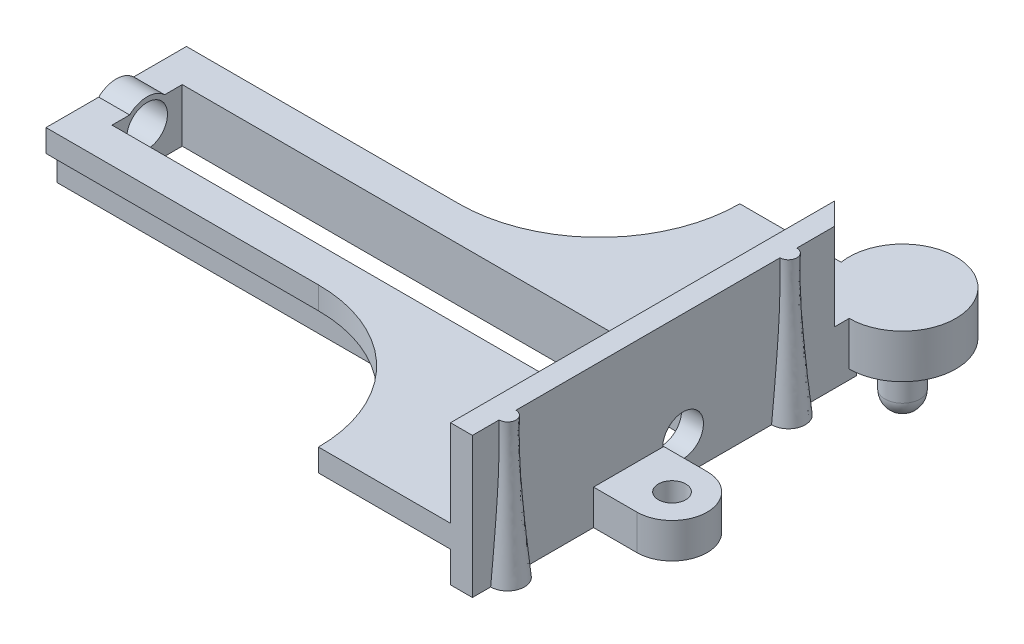
SolidWorks part; units mm, degrees
ref_plane "Alzado" through (0, 0, 0) normal (0, 0, 1) x (1, 0, 0)
ref_plane "Planta" through (0, 0, 0) normal (0, 1, 0) x (1, 0, 0)
ref_plane "Vista lateral" through (0, 0, 0) normal (1, 0, 0) x (0, 0, -1)
sketch "Sketch1" plane through (0, 0, 0) normal (1, 0, 0) x (0, 0, -1)
  line L1 (-10.668, -4.826) -> (10.668, -4.826)
  line L2 (-12.7, 0.762) -> (-12.7, 4.826)
  line L3 (-12.7, 4.826) -> (-3.1623, 4.826)
  line L6 (0, -4.826) -> (0, 12.0832) construction
  line L7 (-10.668, -4.826) -> (-10.668, 0.762)
  line L9 (-10.668, 0.762) -> (-12.7, 0.762)
  line L13 (10.668, 0.762) -> (12.7, 0.762)
  line L14 (10.668, -4.826) -> (10.668, 0.762)
  line L15 (12.7, 4.826) -> (3.1623, 4.826)
  line L16 (12.7, 0.762) -> (12.7, 4.826)
  arc A0 (3.1623, 4.826) -> (-3.1623, 4.826) centre (0, 1.524) ccw
  point P0 (0, 0)
  dimension "D5" = 9.144
extrude "Boss-Extrude1" add sketch "Sketch1" along normal blind 98.552
sketch "Sketch2" plane through (0, 4.826, 0) normal (0, 1, 0) x (1, 0, 0)
  line L0 (0, 0) -> (5.588, 0)
  line L1 (5.588, -6.35) -> (5.588, 6.35)
  line L2 (5.588, 6.35) -> (98.552, 6.35)
  line L3 (98.552, 12.7) -> (98.552, 3.1623) construction
  line L4 (5.588, -6.35) -> (98.552, -6.35)
  line L5 (98.552, -3.1623) -> (98.552, -12.7) construction
  line L6 (98.552, -6.35) -> (98.552, 6.35)
  point P6 (5.588, 0)
  line M6 (98.552, -12.7) -> (98.552, -3.1623)
  line M7 (98.552, -3.1623) -> (0, -3.1623)
  dimension "D1" = 5.588
  dimension "D2" = 12.7
extrude "Cut-Extrude2" cut sketch "Sketch2" against normal through all both and the other way through all contours L1 L4 M6 M7 | L6 L2 L1 M7 region at (52.07, 4.826, -1.5939) region at (52.07, 4.826, 4.7561)
sketch "Sketch3" plane through (0, 4.826, 0) normal (0, 1, 0) x (1, 0, 0)
  line L0 (0, -12.7) -> (49.276, -12.7)
  line L1 (98.552, -12.7) -> (0, -12.7) construction
  line L2 (49.276, -12.7) -> (98.552, -12.7)
  line L3 (98.552, -12.7) -> (98.552, -38.1)
  line L4 (98.552, -38.1) -> (74.676, -38.1)
  arc A0 (74.676, -38.1) -> (49.276, -12.7) centre (49.276, -38.1) ccw
  line M6 (0, -12.7) -> (98.552, -12.7)
  dimension "D2" = 50.8
  dimension "D1" = 49.276
extrude "Boss-Extrude2" add sketch "Sketch3" against normal up to vertex (4.064 mm away) contours A0 L4 L3 M6 region at (83.3406, 4.826, 24.094) up to point (98.552, 0.762, 12.7)
mirror "Mirror1" about plane through (0, 0, 0) normal (0, 0, 1) of "Boss-Extrude2"
sketch "Sketch5" plane through (0, -4.826, 0) normal (0, -1, 0) x (1, 0, 0)
  line L0 (98.552, 0) -> (98.552, 38.1)
  line L1 (98.552, 38.1) -> (98.552, 10.668) construction
  line L2 (98.552, 38.1) -> (102.5144, 38.1)
  line L3 (102.5144, 38.1) -> (102.5144, -31.369)
  line L4 (102.5144, -31.369) -> (98.552, -31.369)
  line L5 (98.552, -10.668) -> (98.552, -38.1) construction
  line L6 (98.552, -31.369) -> (98.552, 0)
  line L7 (102.5144, 38.1) -> (102.5144, 31.75)
  point P4 (0, 0)
  line M9 (98.552, 6.35) -> (98.552, 10.668)
  line M13 (98.552, -10.668) -> (98.552, -6.35)
  dimension "D1" = 3.9624
  dimension "D2" = 69.469
  dimension "D3" = 6.35
extrude "Boss-Extrude3" add sketch "Sketch5" against normal blind 25.4 contours L6 L4 L3 L2 L0 M9 M13 region at (100.5332, -4.826, 3.3655)
sketch "Sketch6" plane through (0, 20.574, 0) normal (0, 1, 0) x (1, 0, 0)
  line L0 (102.5144, -38.1) -> (102.5144, 31.369) construction
  circle A0 centre (102.5144, -31.75) radius 1.524
  point P0 (0, 0)
  dimension "D2" = 3.048
sketch "Sketch7" plane through (0, -4.826, 0) normal (0, -1, 0) x (1, 0, 0)
  circle A0 centre (102.5144, 31.75) radius 3.048
  dimension "D1" = 6.096
  dimension "D2" = 6.35
loft "Loft1" add profiles "Sketch7", "Sketch6" connector at (105.1082, -4.826, 33.3507) connector at (103.6801, 20.574, 30.7683)
sketch "Sketch8" plane through (0, 20.574, 0) normal (0, 1, 0) x (1, 0, 0)
  line L0 (102.5144, -31.75) -> (102.5144, 19.05)
  line L1 (102.5144, -30.226) -> (102.5144, 31.369) construction
  arc A0 (102.5144, -33.274) -> (102.5144, -30.226) centre (102.5144, -31.75) ccw construction
  point P4 (102.5144, -6.35)
  point P5 (0, 0)
  point P6 (0, 0)
  point P7 (0, 0)
  dimension "D1" = 50.8
ref_plane "Plane1" through (0, 0, 6.35) normal (0, 0, -1) x (-1, 0, 0)
mirror "Mirror2" about plane through (0, 0, 6.35) normal (0, 0, -1) of "Loft1"
sketch "Sketch9" plane through (5.588, 0, 0) normal (1, 0, 0) x (0, 0, -1)
  line L0 (-6.35, -4.826) -> (6.35, -4.826) construction
  circle A0 centre (0, 1.524) radius 3.683
  dimension "D2" = 7.366
  dimension "D1" = 6.35
extrude "Cut-Extrude3" cut sketch "Sketch9" along normal through all both and the other way through all
sketch "Sketch10" plane through (102.5144, 0, 0) normal (1, 0, 0) x (0, 0, -1)
  line L0 (0, 1.524) -> (-16.195, 1.524)
  line L1 (-16.195, 1.524) -> (-16.195, -4.826)
  line L2 (-28.702, -4.826) -> (16.002, -4.826) construction
  line L3 (-22.545, -4.826) -> (-9.845, -4.826)
  point P9 (-16.195, -4.826)
  dimension "D1" = 16.195
  dimension "D2" = 12.7
sketch "Sketch11" plane through (0, -4.826, 0) normal (0, -1, 0) x (1, 0, 0)
  line L0 (102.5144, 16.195) -> (110.363, 16.195)
  line L2 (102.5144, 16.195) -> (102.5144, 9.845)
  line L4 (110.363, 3.495) -> (102.5144, 3.495)
  line L5 (102.5144, 28.702) -> (102.5144, -16.002) construction
  line L6 (102.5144, 9.845) -> (102.5144, 3.495)
  arc A0 (110.363, 3.495) -> (110.363, 16.195) centre (110.363, 9.845) ccw
  circle A1 centre (110.363, 9.845) radius 2.479
  dimension "D2" = 4.9581
  dimension "D1" = 7.8486
extrude "Boss-Extrude4" add sketch "Sketch11" against normal blind 6.35
sketch "Sketch12" plane through (0, 4.826, 0) normal (0, 1, 0) x (1, 0, 0)
  line L8 (5.588, 3.1623) -> (5.588, 6.35)
  line L9 (5.588, 6.35) -> (98.552, 6.35)
  line L10 (98.552, 6.35) -> (98.552, 31.369)
  line L11 (98.552, 31.369) -> (98.552, 38.1)
  line L12 (98.552, 38.1) -> (74.676, 38.1)
  line L13 (49.276, 12.7) -> (0, 12.7)
  line L14 (0, 12.7) -> (0, 3.1623)
  line L15 (0, 3.1623) -> (5.588, 3.1623)
  line L16 (5.588, 3.1623) -> (5.588, 6.35)
  line L17 (5.588, 6.35) -> (98.552, 6.35)
  line L18 (98.552, 6.35) -> (98.552, 31.369)
  line L19 (98.552, 31.369) -> (98.552, 38.1)
  line L20 (98.552, 38.1) -> (74.676, 38.1)
  line L21 (49.276, 12.7) -> (0, 12.7)
  line L22 (0, 12.7) -> (0, 3.1623)
  line L23 (0, 3.1623) -> (5.588, 3.1623)
  arc A1 (49.276, 12.7) -> (74.676, 38.1) centre (49.276, 38.1) ccw
  arc A2 (49.276, 12.7) -> (74.676, 38.1) centre (49.276, 38.1) ccw
  dimension "D1" = 0
sketch "Sketch13" plane through (0, 4.826, 0) normal (0, 1, 0) x (1, 0, 0)
  line L0 (102.5144, 0) -> (102.5144, -16.195) construction
  line L1 (102.5144, 39.685) -> (102.5144, -16.195)
  line L8 (5.588, 3.1623) -> (5.588, 6.35)
  line L9 (5.588, 6.35) -> (98.552, 6.35)
  line L10 (98.552, 6.35) -> (98.552, 31.369)
  line L11 (98.552, 31.369) -> (98.552, 38.1)
  line L12 (98.552, 38.1) -> (74.676, 38.1)
  line L13 (49.276, 12.7) -> (0, 12.7)
  line L14 (0, 12.7) -> (0, 3.1623)
  line L15 (0, 3.1623) -> (5.588, 3.1623)
  line L16 (5.588, 3.1623) -> (5.588, 6.35)
  line L17 (5.588, 6.35) -> (98.552, 6.35)
  line L18 (98.552, 6.35) -> (98.552, 31.369)
  line L19 (98.552, 31.369) -> (98.552, 38.1)
  line L20 (98.552, 38.1) -> (74.676, 38.1)
  line L21 (49.276, 12.7) -> (0, 12.7)
  line L22 (0, 12.7) -> (0, 3.1623)
  line L23 (0, 3.1623) -> (5.588, 3.1623)
  arc A1 (49.276, 12.7) -> (74.676, 38.1) centre (49.276, 38.1) ccw
  arc A2 (49.276, 12.7) -> (74.676, 38.1) centre (49.276, 38.1) ccw
  point P17 (102.5144, 39.685)
  dimension "D2" = 55.88
  dimension "D1" = 0
ref_plane "Plane2" through (0, 0, -39.685) normal (0, 0, -1) x (-1, 0, 0)
sketch "Sketch14" plane through (0, 0, -39.685) normal (0, 0, -1) x (-1, 0, 0)
  line L0 (-102.5144, 4.826) -> (-102.5144, -14.224)
  line L1 (-102.5144, 4.826) -> (-102.5144, -16.2891) construction
  line L2 (-102.5144, 4.826) -> (-112.1664, 4.826)
  line L3 (-112.1664, 4.826) -> (-112.1664, -3.0988)
  line L4 (-112.1664, -3.0988) -> (-109.8571, -3.0988)
  line L5 (-109.8571, -3.0988) -> (-109.8571, 1.4732)
  line L6 (-109.8571, 1.4732) -> (-105.6894, 1.4732)
  line L7 (-105.6894, 1.4732) -> (-105.6894, -14.224)
  line L8 (-105.6894, -14.224) -> (-102.5144, -14.224)
  dimension "D1" = 19.05
  dimension "D2" = 9.652
  dimension "D3" = 7.9248
  dimension "D4" = 3.175
  dimension "D5" = 4.572
revolve "Revolve1" add sketch "Sketch14" angle 360 about L1
fillet "Fillet1" radius 3.175 1 edges at (99.3394, -14.224, -39.685)
sketch "Sketch15" plane through (0, 20.574, 0) normal (0, 1, 0) x (1, 0, 0)
  line L0 (98.552, 31.369) -> (102.5144, 27.4066)
  line L2 (98.552, 31.369) -> (98.552, -38.1) construction
  line L3 (98.552, 31.369) -> (102.5144, 31.369)
  line L4 (102.5144, 31.369) -> (102.5144, 27.4066)
  line L5 (102.5144, 20.574) -> (102.5144, 31.369) construction
  dimension "D1" = 45
extrude "Cut-Extrude4" cut sketch "Sketch15" against normal up to vertex (15.748 mm away) up to point (102.5144, 4.826, -30.033)
